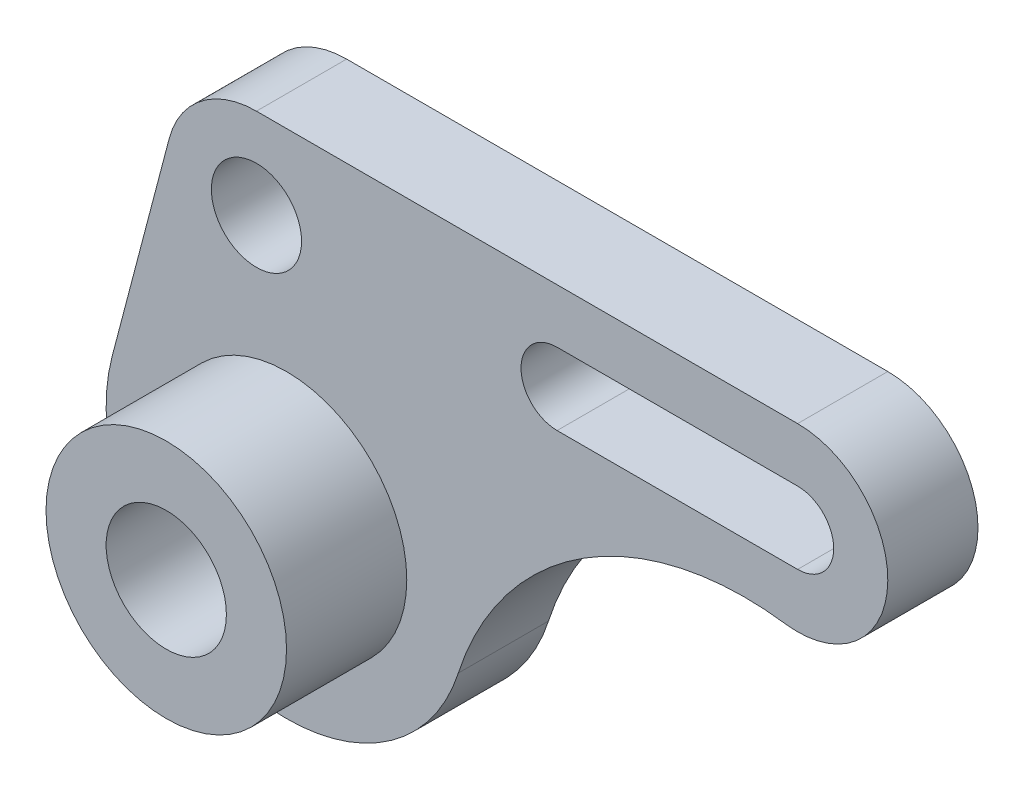
SolidWorks part; units mm, degrees
ref_plane "Front Plane" through (0, 0, 0) normal (0, 0, 1) x (1, 0, 0)
ref_plane "Top Plane" through (0, 0, 0) normal (0, 1, 0) x (1, 0, 0)
ref_plane "Right Plane" through (0, 0, 0) normal (1, 0, 0) x (0, 0, -1)
sketch "Sketch1" plane through (0, 0, 0) normal (0, 0, 1) x (1, 0, 0)
  line L0 (0, 0) -> (0, 27.9066) construction
  line L1 (40, 0) -> (40, 27.9066) construction
  line L2 (-50, 0) -> (-50, 27.9066) construction
  line L3 (-70.5661, 0) -> (58.8279, 0) construction
  line L4 (0, 6) -> (40, 6)
  line L5 (0, -6) -> (40, -6)
  line L6 (40, 15) -> (-50, 15)
  line L7 (-77.2337, -40) -> (0, -40) construction
  line L8 (-45, -20.0578) -> (-45, -63.7707) construction
  line L9 (-64.5077, 3.8115) -> (-74.0153, -32.3769)
  arc A0 (37.9665, -14.8615) -> (40, 15) centre (40, 0) ccw
  arc A1 (40, -6) -> (40, 6) centre (40, 0) ccw
  arc A2 (0, 6) -> (0, -6) centre (0, 0) ccw
  arc A3 (-50, 15) -> (-64.5077, 3.8115) centre (-50, 0) ccw
  circle A4 centre (-50, 0) radius 7.5
  circle A5 centre (-45, -40) radius 20
  circle A6 centre (-45, -40) radius 10
  arc A7 (-74.0153, -32.3769) -> (-16.4294, -49.15) centre (-45, -40) ccw
  arc A8 (37.9665, -14.8615) -> (-16.4294, -49.15) centre (31.1882, -64.3999) ccw
  dimension "D3" = 30
  dimension "D4" = 12
  dimension "D5" = 12
  dimension "D6" = 15
  dimension "D9" = 40
  dimension "D10" = 20
  dimension "D11" = 60
  dimension "D12" = 30
  dimension "D1" = 40
  dimension "D2" = 50
  dimension "D7" = 40
  dimension "D8" = 85
extrude "Boss-Extrude1" add sketch "Sketch1" along normal blind 15 contours A8 A0 L6 A3 L9 A7 A5 A4 A2 L4 A1 L5 region at (-20.8742, -15.7377, 0)
extrude "Boss-Extrude2" add sketch "Sketch1<3>" along normal blind 35 contours A5 A6 region at (-64.4343, -40, 0)
sketch "Sketch1<3>" plane through (0, 0, 0) normal (0, 0, 1) x (1, 0, 0) same geometry as "Sketch1"
